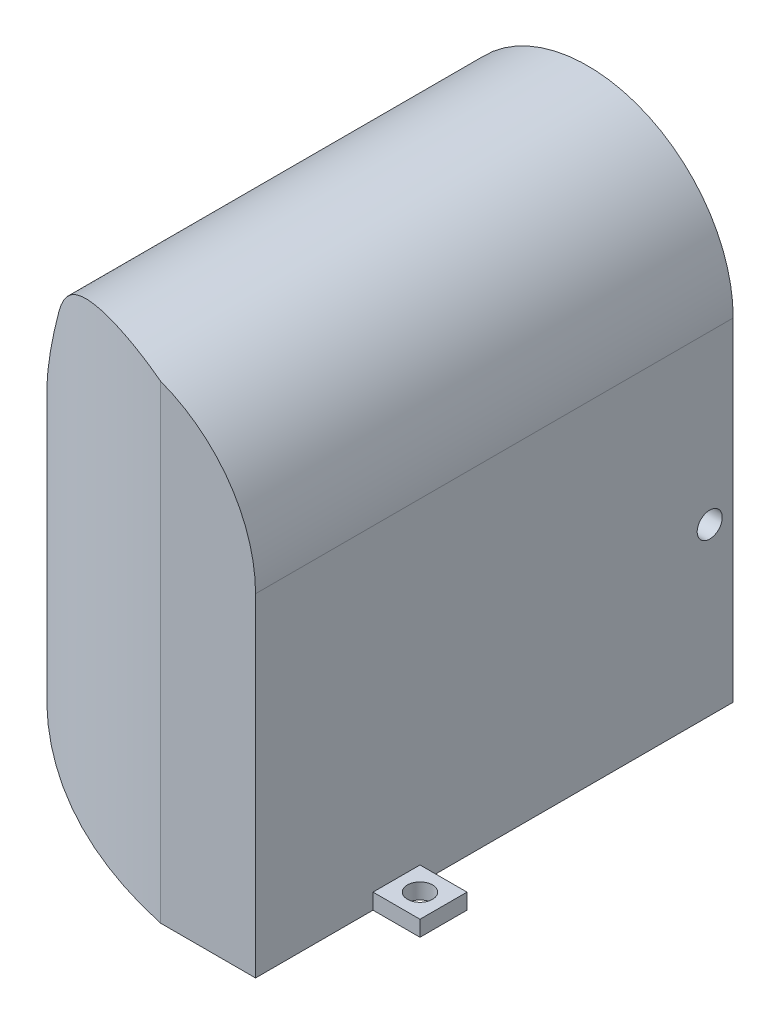
SolidWorks part; units mm, degrees
ref_plane "정면" through (0, 0, 0) normal (0, 0, 1) x (1, 0, 0)
ref_plane "윗면" through (0, 0, 0) normal (0, 1, 0) x (1, 0, 0)
ref_plane "우측면" through (0, 0, 0) normal (1, 0, 0) x (0, 0, -1)
sketch "스케치1" plane through (0, 0, 0) normal (0, 0, 1) x (1, 0, 0)
  line L0 (40, 0) -> (-20, 0)
  line L1 (0, 0) -> (40, 0)
  line L4 (40, 0) -> (40, 42.5)
  line L6 (-20, 0) -> (6.8435, 50.7314)
  arc A1 (40, 42.5) -> (6.8435, 50.7314) centre (22.4, 42.5) ccw
  dimension "D1" = 35.2
  dimension "D2" = 42.5
  dimension "D3" = 60
extrude "보스-돌출1" add sketch "스케치1" along normal blind 60 contours L4 L0 region at (16.5295, 25.4378, 0)
sketch "스케치6" plane through (0, 0, 0) normal (0, -1, 0) x (-1, 0, 0)
  line L0 (-40, 0) -> (20, 0) construction
  line L1 (-40, -60) -> (-40, 0) construction
  line L5 (-28.985, -60) -> (20, -60)
  line L6 (20, -10.0372) -> (20, -60)
  arc A0 (-28.985, -60) -> (20, -10.0372) centre (-42.76, 2.5) ccw
  dimension "D1" = 2.5
  dimension "D3" = 128
  dimension "D2" = 2.76
extrude "컷-돌출5" cut sketch "스케치6" against normal through all
shell "쉘1" thickness 1 removed face at (17.5156, 26.5493, 0) removed face at (12.3105, 0, 27.4648) outward yes
sketch "스케치2" plane through (0, 0, 0) normal (0, 0, -1) x (-1, 0, 0)
  line L0 (-41, 0) -> (-41, 42.5) construction
  line L1 (-41, 24.15) -> (-38, 24.15)
  line L2 (-41, 24.15) -> (-41, 18.35)
  line L3 (-41, 18.35) -> (-38, 18.35)
  line L4 (-38, 24.15) -> (-38, 18.35)
  line L5 (6.0716, 28.4613) -> (8.7843, 23.3347)
  line L6 (6.0716, 28.4613) -> (3.42, 27.0582)
  line L7 (8.7843, 23.3347) -> (6.1326, 21.9316)
  line L8 (3.42, 27.0582) -> (6.1326, 21.9316)
  line L9 (21.1314, 0) -> (-5.9596, 51.1991) construction
  line L10 (-41, 0) -> (-40, 0) construction
  dimension "D1" = 5.8
  dimension "D2" = 5.8
  dimension "D3" = 18.35
  dimension "D4" = 26.4
  dimension "D5" = 3
  dimension "D6" = 3
extrude "보스-돌출2" add sketch "스케치2" against normal blind 6
sketch "스케치3" plane through (38, 0, 0) normal (-1, 0, 0) x (0, 0, 1)
  line L0 (6, 24.15) -> (0, 24.15) construction
  line L1 (6, 18.35) -> (6, 24.15) construction
  circle A0 centre (3, 21.1482) radius 1.6
  dimension "D1" = 3.2
  dimension "D2" = 3.0018
  dimension "D3" = 3
extrude "컷-돌출1" cut sketch "스케치3" against normal through all
sketch "스케치4" plane through (-13.8575, 7.3324, 0) normal (0.8839, -0.4677, 0) x (0, 0, -1)
  line L0 (-6, 22.317) -> (0, 22.317) construction
  line L1 (0, 22.317) -> (0, 16.517) construction
  circle A0 centre (-3, 19.317) radius 1.6
  dimension "D1" = 3.2
  dimension "D2" = 3
  dimension "D3" = 3
extrude "컷-돌출2" cut sketch "스케치4" against normal through all
chamfer "모따기1" distance 0.2 angle 45 4 edges at (-6.1326, 21.9316, 3) (-3.42, 27.0582, 3) (38, 18.35, 3) (38, 24.15, 3)
sketch "스케치5" plane through (0, 0, 0) normal (0, -1, 0) x (1, 0, 0)
  line L7 (40, 46) -> (40, 40)
  line L8 (40, 46) -> (47, 46)
  line L9 (40, 40) -> (47, 40)
  line L10 (47, 46) -> (47, 40)
  line L11 (40, 60) -> (40, 0) construction
  line L12 (6.8435, 0) -> (40, 0) construction
  circle A0 centre (44, 43) radius 1.6
  dimension "D4" = 3.2
  dimension "D6" = 3
  dimension "D1" = 40
  dimension "D2" = 6
  dimension "D3" = 7
  dimension "D5" = 3
extrude "보스-돌출3" add sketch "스케치5" against normal blind 2
